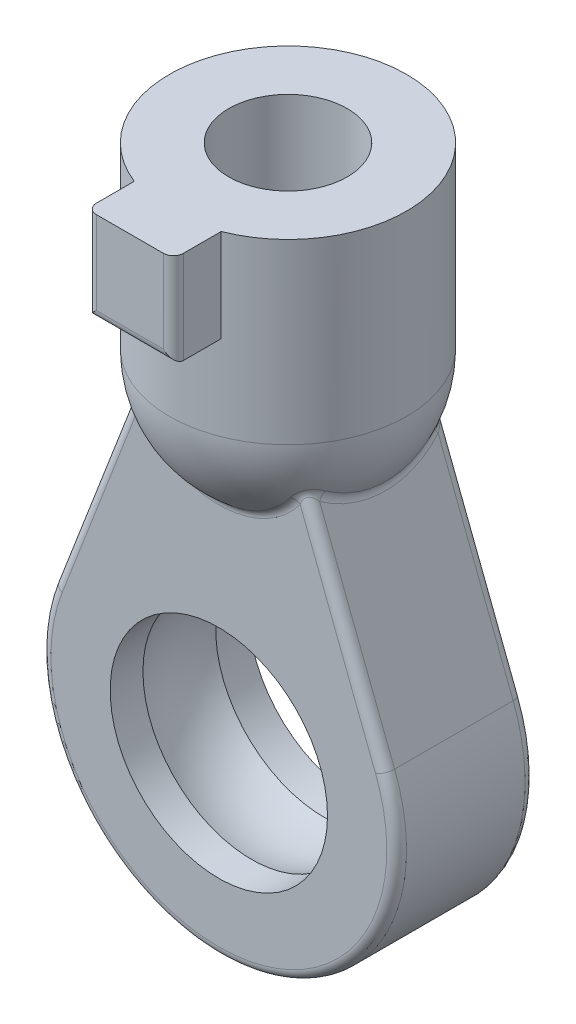
SolidWorks part; units mm, degrees
ref_plane "Front Plane" through (0, 0, 0) normal (0, 0, 1) x (1, 0, 0)
ref_plane "Top Plane" through (0, 0, 0) normal (0, 1, 0) x (1, 0, 0)
ref_plane "Right Plane" through (0, 0, 0) normal (1, 0, 0) x (0, 0, -1)
sketch "Sketch1" plane through (0, 0, 0) normal (0, 0, 1) x (1, 0, 0)
  line L0 (0, 12.5) -> (4.1983, 1.62)
  line L1 (0, 0) -> (0, 12.5) construction
  line L2 (0, 12.5) -> (-4.1983, 1.62)
  line L5 (0, -8.1743) -> (0, 16.2407) construction
  arc A1 (-4.1983, 1.62) -> (4.1983, 1.62) centre (0, 0) ccw
  dimension "D1" = 9
  dimension "D3" = 12.5
extrude "Boss-Extrude1" add sketch "Sketch1" along normal mid plane 3.5
sketch "Sketch2" plane through (0, 0, 0) normal (0, 0, 1) x (1, 0, 0)
  line L0 (0, -5.5022) -> (0, 13.5225) construction
  line L1 (0, 2.9) -> (0, -2.9)
  arc A0 (0, 2.9) -> (0, -2.9) centre (0, 0) cw
  dimension "D1" = 2.9
revolve "Cut-Revolve1" cut sketch "Sketch2" angle 360 about L0
sketch "Sketch3" plane through (0, 0, 0) normal (0, 0, 1) x (1, 0, 0)
  line L0 (0, 0) -> (0, 13.2243) construction
  line L1 (0, 12.5) -> (3, 12.5)
  line L2 (3, 12.5) -> (3, 8)
  line L3 (0, 12.5) -> (0, 5)
  arc A0 (0, 5) -> (3, 8) centre (0, 8) ccw
  dimension "D3" = 3
  dimension "D1" = 3
  dimension "D2" = 4.5
revolve "Revolve2" add sketch "Sketch3" angle 360 about L0
sketch "Sketch6" plane through (0, 0, 0) normal (0, 0, 1) x (1, 0, 0)
  line L0 (0, 12.5) -> (0, 10.15) construction
  line L1 (3, 12.5) -> (-3, 12.5) construction
  line L2 (-1.1, 12.5) -> (-1.1, 10.15)
  line L3 (1.1, 12.5) -> (1.1, 10.15)
  line L4 (-1.1, 12.5) -> (1.1, 12.5)
  line L5 (-1.1, 10.15) -> (1.1, 10.15)
  dimension "D1" = 2.35
  dimension "D2" = 1.1
  dimension "D3" = 1.1
extrude "Boss-Extrude2" add sketch "Sketch6" along normal blind 4
sketch "Sketch4" plane through (0, 12.5, 0) normal (0, 1, 0) x (1, 0, 0)
  circle A0 centre (0, 0) radius 1.5
  dimension "D1" = 3
extrude "Cut-Extrude1" cut sketch "Sketch4" against normal blind 4.5
sketch "Sketch7" plane through (0, 0, 1.75) normal (0, 0, 1) x (1, 0, 0)
  circle A0 centre (0, 0) radius 2.75
  dimension "D1" = 5.5
extrude "Cut-Extrude2" cut sketch "Sketch7" against normal through all
fillet "Fillet1" radius 0.25 13 edges at (-3.1825, 4.2525, -1.75) (0, -4.5, -1.75) (-3.1825, 4.2525, 1.75) (0, -4.5, 1.75) (-1.1, 11.325, 4) (0, 10.15, 4) (1.1, 11.325, 4) (0, 5.5633, -1.75) (-2.4204, 6.2275, 0) (0, 5.5633, 1.75) (2.4204, 6.2275, 0) (3.1825, 4.2525, -1.75) (3.1825, 4.2525, 1.75)
sketch "Sketch8" plane through (0, 0, 0) normal (1, 0, 0) x (0, 0, -1)
  line L0 (0, 0) -> (8.6305, 0) construction
